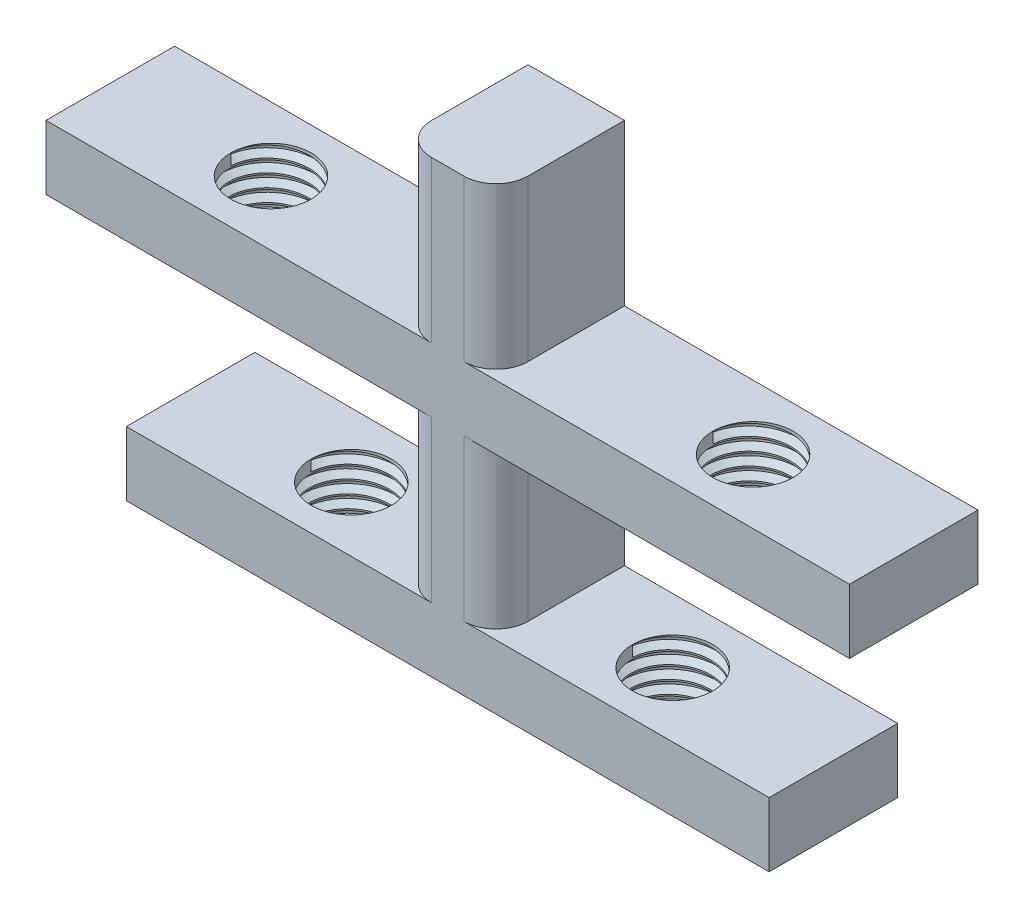
SolidWorks part; units mm, degrees
ref_plane "Front Plane" through (0, 0, 0) normal (0, 0, 1) x (1, 0, 0)
ref_plane "Top Plane" through (0, 0, 0) normal (0, 1, 0) x (1, 0, 0)
ref_plane "Right Plane" through (0, 0, 0) normal (1, 0, 0) x (0, 0, -1)
sketch "Sketch1" plane through (0, 0, 0) normal (0, 1, 0) x (1, 0, 0)
  line L0 (0, 115.9667) -> (0, -129.5) construction
  line L1 (-100, 20) -> (100, 20)
  line L2 (-100, 20) -> (-100, -20)
  line L3 (-100, -20) -> (100, -20)
  line L4 (100, 20) -> (100, -20)
  line L5 (-100, 20) -> (100, -20) construction
  line L6 (-100, -20) -> (100, 20) construction
  circle A0 centre (-50, 0) radius 12.5
  circle A1 centre (50, 0) radius 12.5
  point P0 (0, 0)
  dimension "D4" = 25
  dimension "D1" = 40
  dimension "D2" = 200
  dimension "D3" = 50
extrude "Boss-Extrude1" add sketch "Sketch1" along normal blind 20
sketch "Sketch2" plane through (0, 20, 0) normal (0, 1, 0) x (1, 0, 0)
  line L0 (0, 62.604) -> (0, -93.4223) construction
  line L1 (-100, -20) -> (100, -20) construction
  line L2 (-15, 20) -> (15, 20)
  line L3 (-15, 20) -> (-15, -20)
  line L4 (-15, -20) -> (15, -20)
  line L5 (15, 20) -> (15, -20)
  line L6 (-15, 20) -> (15, -20) construction
  line L7 (-15, -20) -> (15, 20) construction
  point P3 (0, 0)
  dimension "D1" = 30
extrude "Boss-Extrude2" add sketch "Sketch2" along normal blind 50
fillet "Fillet1" radius 10 2 edges at (15, 45, 20) (-15, 45, 20)
thread "Thread1" pitch 4 method cut profile "Thread Profile1" start angle 0, offset 0, length 0, pitch 4, diameter 25
ref_plane "Plane3" through (-62.5, 20, 0) normal (0, 0, -1) x (1, 0, 0)
sketch "Thread Profile1" plane through (-62.5, 20, 0) normal (0, 0, -1) x (1, 0, 0)
  line L0 (0, 0) -> (0, 4) construction
  line L11 (0, 0) -> (0, 3.5)
  line L12 (0, 3.5) -> (-2.1651, 2.25)
  line L13 (-2.1651, 2.25) -> (-2.1651, 1.25)
  line L15 (-2.1651, 1.25) -> (0, 0)
  line L17 (-2.1651, 1.75) -> (0, 1.75) construction
  point P2 (0, 0)
  dimension "Pitch" = 4
  dimension "Profile_Angle" = 60
  dimension "Profile_Land" = 1
  dimension "Profile_Height" = 2.1651
thread "Thread2" pitch 4 method cut profile "Thread Profile2" start angle 0, offset 0, length 0, pitch 4, diameter 25
ref_plane "Plane4" through (37.5, 20, 0) normal (0, 0, -1) x (1, 0, 0)
sketch "Thread Profile2" plane through (37.5, 20, 0) normal (0, 0, -1) x (1, 0, 0)
  line L0 (0, 0) -> (0, 4) construction
  line L11 (0, 0) -> (0, 3.5)
  line L12 (0, 3.5) -> (-2.1651, 2.25)
  line L13 (-2.1651, 2.25) -> (-2.1651, 1.25)
  line L15 (-2.1651, 1.25) -> (0, 0)
  line L17 (-2.1651, 1.75) -> (0, 1.75) construction
  point P2 (0, 0)
  dimension "Pitch" = 4
  dimension "Profile_Angle" = 60
  dimension "Profile_Land" = 1
  dimension "Profile_Height" = 2.1651
sketch "Sketch8" plane through (0, 70, 0) normal (0, 1, 0) x (1, 0, 0)
  line L0 (0, 69.9197) -> (0, -90.4108) construction
  line L1 (-125, 20) -> (100, 20)
  line L2 (-125, 20) -> (-125, -20)
  line L3 (-125, -20) -> (100, -20)
  line L5 (-45, 69.9197) -> (-45, -84.7728) construction
  line L6 (45, 67.8054) -> (45, -90.4108) construction
  line L7 (-15, 20) -> (-15, -10) construction
  line L8 (15, -10) -> (15, 20) construction
  line L9 (100, 20) -> (125, 20)
  line L10 (125, 20) -> (125, -20)
  line L11 (125, -20) -> (100, -20)
  circle A0 centre (-75, 0) radius 12.5
  circle A1 centre (75, 0) radius 12.5
  point P0 (0, 0)
  dimension "D3" = 25
  dimension "D1" = 30
  dimension "D2" = 30
  dimension "D4" = 75
  dimension "D5" = 125
  dimension "D6" = 125
extrude "Boss-Extrude4" add sketch "Sketch8" along normal blind 20
sketch "Sketch9" plane through (0, 90, 0) normal (0, 1, 0) x (1, 0, 0)
  line L0 (-125, -20) -> (125, -20) construction
  line L1 (-15, 20) -> (15, 20)
  line L2 (-15, 20) -> (-15, -20)
  line L3 (-15, -20) -> (15, -20)
  line L4 (15, 20) -> (15, -20)
  line L5 (-15, 20) -> (15, -20) construction
  line L6 (-15, -20) -> (15, 20) construction
  point P0 (0, 0)
  dimension "D1" = 30
  dimension "D2" = 40
extrude "Boss-Extrude5" add sketch "Sketch9" along normal blind 50
fillet "Fillet2" radius 10 2 edges at (15, 115, 20) (-15, 115, 20)
thread "Thread3" pitch 4 method cut profile "Thread Profile3" start angle 0, offset 0, length 0, pitch 4, diameter 25
ref_plane "Plane5" through (-87.5, 90, 0) normal (0, 0, -1) x (1, 0, 0)
sketch "Thread Profile3" plane through (-87.5, 90, 0) normal (0, 0, -1) x (1, 0, 0)
  line L0 (0, 0) -> (0, 4) construction
  line L11 (0, 0) -> (0, 3.5)
  line L12 (0, 3.5) -> (-2.1651, 2.25)
  line L13 (-2.1651, 2.25) -> (-2.1651, 1.25)
  line L15 (-2.1651, 1.25) -> (0, 0)
  line L17 (-2.1651, 1.75) -> (0, 1.75) construction
  point P2 (0, 0)
  dimension "Pitch" = 4
  dimension "Profile_Angle" = 60
  dimension "Profile_Land" = 1
  dimension "Profile_Height" = 2.1651
thread "Thread4" pitch 4 method cut profile "Thread Profile4" start angle 0, offset 0, length 0, pitch 4, diameter 25
ref_plane "Plane6" through (62.5, 90, 0) normal (0, 0, -1) x (1, 0, 0)
sketch "Thread Profile4" plane through (62.5, 90, 0) normal (0, 0, -1) x (1, 0, 0)
  line L0 (0, 0) -> (0, 4) construction
  line L11 (0, 0) -> (0, 3.5)
  line L12 (0, 3.5) -> (-2.1651, 2.25)
  line L13 (-2.1651, 2.25) -> (-2.1651, 1.25)
  line L15 (-2.1651, 1.25) -> (0, 0)
  line L17 (-2.1651, 1.75) -> (0, 1.75) construction
  point P2 (0, 0)
  dimension "Pitch" = 4
  dimension "Profile_Angle" = 60
  dimension "Profile_Land" = 1
  dimension "Profile_Height" = 2.1651
